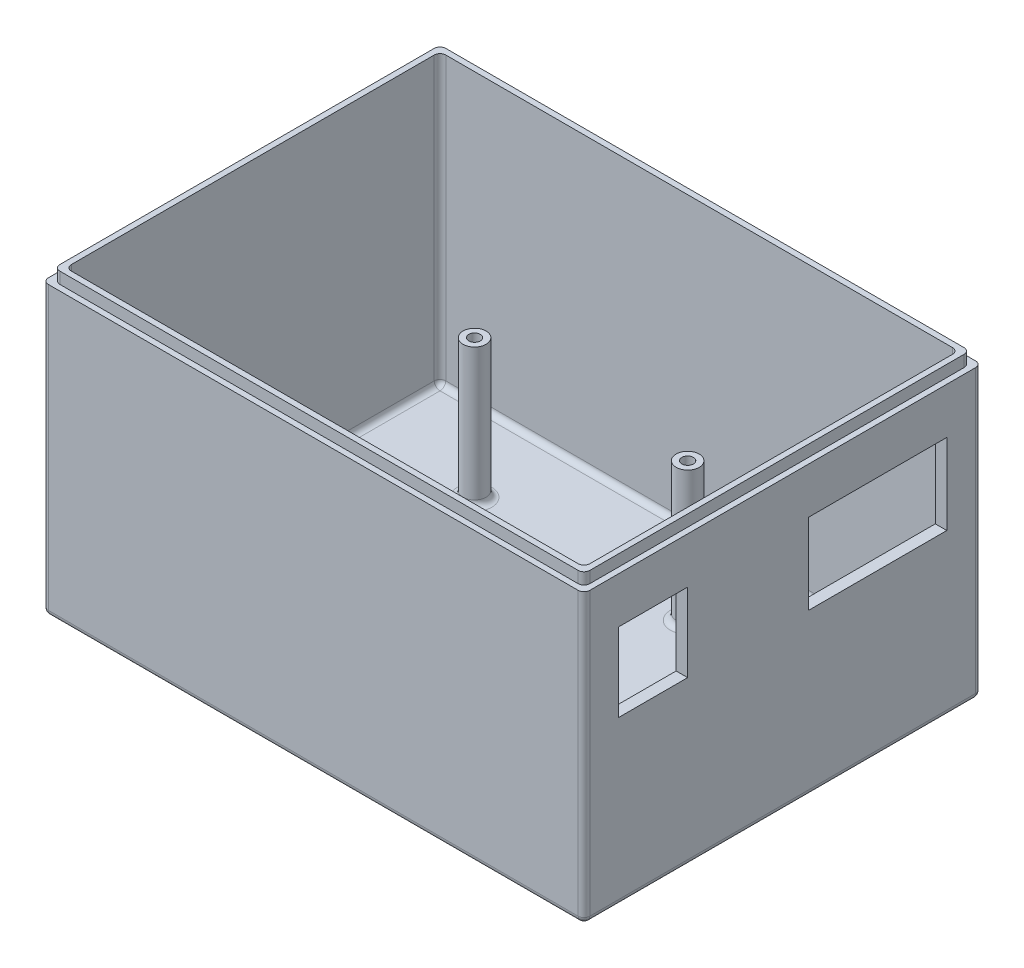
SolidWorks part; units mm, degrees
ref_plane "Front Plane" through (0, 0, 0) normal (0, 0, 1) x (1, 0, 0)
ref_plane "Top Plane" through (0, 0, 0) normal (0, 1, 0) x (1, 0, 0)
ref_plane "Right Plane" through (0, 0, 0) normal (1, 0, 0) x (0, 0, -1)
sketch "Sketch1" plane through (0, 0, 0) normal (0, 1, 0) x (1, 0, 0)
  line L1 (45, -32.5) -> (-45, -32.5)
  line L2 (45, -32.5) -> (45, 32.5)
  line L3 (45, 32.5) -> (-45, 32.5)
  line L4 (-45, -32.5) -> (-45, 32.5)
  line L5 (45, -32.5) -> (-45, 32.5) construction
  line L6 (45, 32.5) -> (-45, -32.5) construction
  point P0 (0, 0)
  dimension "D1" = 90
  dimension "D2" = 65
extrude "Boss-Extrude1" add sketch "Sketch1" along normal blind 50
shell "Shell1" thickness 2 removed face at (0, 50, 0) outward yes
sketch "Sketch2" plane through (0, 0, 0) normal (0, 1, 0) x (1, 0, 0)
  line L0 (45, -32.5) -> (45, 32.5) construction
  circle A0 centre (40, 0) radius 2.5
  circle A1 centre (-40, 0) radius 2.5
  dimension "D2" = 5
  dimension "D1" = 5
extrude "Boss-Extrude2" add sketch "Sketch2" along normal blind 10
sketch "Sketch3" plane through (0, 0, 0) normal (0, 1, 0) x (1, 0, 0)
  line L0 (45, 32.5) -> (-45, 32.5) construction
  line L1 (45, -32.5) -> (45, 32.5) construction
  line L2 (-45, -32.5) -> (45, -32.5) construction
  line L3 (-45, 32.5) -> (-45, -32.5) construction
  circle A0 centre (40, 27.5) radius 2.5
  circle A1 centre (-40, -27.5) radius 2.6728
  dimension "D3" = 5
  dimension "D1" = 5
  dimension "D2" = 5
  dimension "D4" = 5
  dimension "D5" = 5
extrude "Boss-Extrude3" add sketch "Sketch3" along normal blind 4
sketch "Sketch5" plane through (0, 4, 0) normal (0, 1, 0) x (1, 0, 0)
  circle A0 centre (40, 27.5) radius 1
  circle A1 centre (-40, -27.5) radius 1
  dimension "D1" = 2
  dimension "D2" = 2
extrude "Cut-Extrude1" cut sketch "Sketch5" against normal blind 3
sketch "Sketch7" plane through (0, 0, 0) normal (0, 1, 0) x (1, 0, 0)
  line L0 (-45, -32.5) -> (45, -32.5) construction
  line L1 (45, 32.5) -> (-45, 32.5) construction
  line L2 (-45, 32.5) -> (-45, -32.5) construction
  circle A0 centre (-25, -18.5) radius 2
  circle A1 centre (-25, 18.5) radius 2
  circle A2 centre (12, 18.5) radius 2
  circle A3 centre (12, -18.5) radius 2
  dimension "D1" = 14
  dimension "D2" = 4
  dimension "D4" = 4
  dimension "D6" = 20
  dimension "D7" = 20
  dimension "D3" = 14
  dimension "D5" = 37
  dimension "D8" = 37
extrude "Boss-Extrude5" add sketch "Sketch7" along normal blind 24 contours A2 | A0 | A1 | A3
sketch "Sketch11" plane through (0, 24, 0) normal (0, 1, 0) x (1, 0, 0)
  circle A0 centre (12, 18.5) radius 1
  circle A1 centre (-25, 18.5) radius 1
  circle A2 centre (-25, -18.5) radius 1
  circle A3 centre (12, -18.5) radius 1
  dimension "D1" = 2
  dimension "D2" = 2
  dimension "D3" = 2
  dimension "D4" = 2
extrude "Cut-Extrude2" cut sketch "Sketch11" against normal blind 4
sketch "Sketch12" plane through (47, 0, 0) normal (1, 0, 0) x (0, 0, -1)
  line L1 (28.5, 40) -> (4.5, 40)
  line L2 (28.5, 40) -> (28.5, 26)
  line L3 (28.5, 26) -> (4.5, 26)
  line L4 (4.5, 40) -> (4.5, 26)
  line L7 (-34.5, 50) -> (34.5, 50) construction
  line L9 (-28.5, 40) -> (-16.5, 40)
  line L10 (-28.5, 40) -> (-28.5, 26.378)
  line L11 (-28.5, 26.378) -> (-16.5, 26.378)
  line L12 (-16.5, 40) -> (-16.5, 26.378)
  line L13 (32.5, 50) -> (32.5, 0) construction
  line L14 (-32.5, 50) -> (-32.5, 0) construction
  dimension "D1" = 4
  dimension "D2" = 14
  dimension "D3" = 10
  dimension "D4" = 24
  dimension "D5" = 4
  dimension "D6" = 12
extrude "Cut-Extrude3" cut sketch "Sketch12" against normal blind 4
sketch "Sketch13" plane through (0, 50, 0) normal (0, 1, 0) x (1, 0, 0)
  line L14 (46, -33.5) -> (46, 33.5)
  line L15 (-46, -33.5) -> (46, -33.5)
  line L16 (-46, 33.5) -> (-46, -33.5)
  line L17 (46, 33.5) -> (-46, 33.5)
  line L18 (46, -33.5) -> (46, 33.5)
  line L19 (-46, -33.5) -> (46, -33.5)
  line L20 (-46, 33.5) -> (-46, -33.5)
  line L21 (46, 33.5) -> (-46, 33.5)
  dimension "D1" = 1
extrude "Cut-Extrude4" cut sketch "Sketch13" against normal blind 2 flip side to cut
fillet "Fillet1" radius 1 4 edges at (0, 0, -32.5) (45, 0, 0) (0, 0, 32.5) (-45, 0, 0)
fillet "Fillet2" radius 1 8 edges at (44.7071, 0.2929, 32.2071) (44.7071, 0.2929, -32.2071) (-44.7071, 0.2929, 32.2071) (-44.7071, 0.2929, -32.2071) (45, 25.5, 32.5) (45, 25.5, -32.5) (-45, 25.5, 32.5) (-45, 25.5, -32.5)
fillet "Fillet3" radius 1 8 edges at (-40, 0, 30.1728) (40, 0, -25) (40, 0, 2.5) (12, 0, 20.5) (12, 0, -16.5) (-25, 0, 20.5) (-25, 0, -16.5) (-40, 0, -2.5)
fillet "Fillet4" radius 1 8 edges at (0, -2, 34.5) (-47, 23, 34.5) (-47, -2, 0) (-47, 23, -34.5) (0, -2, -34.5) (47, 23, -34.5) (47, -2, 0) (47, 23, 34.5)
fillet "Fillet5" radius 1 4 edges at (-46, 49, 33.5) (-46, 49, -33.5) (46, 49, -33.5) (46, 49, 33.5)
fillet "Fillet6" radius 1 4 edges at (-25, 20, 19.5) (-25, 20, -17.5) (12, 20, -17.5) (12, 20, 19.5)
fillet "Fillet7" radius 1 2 edges at (-40, 1, 28.5) (40, 1, -26.5)
sketch "Sketch15" plane through (0, 10, 0) normal (0, 1, 0) x (1, 0, 0)
  circle A0 centre (-40, 0) radius 1.25
  circle A1 centre (40, 0) radius 1.25
  dimension "D1" = 2.5
  dimension "D2" = 2.5
extrude "Cut-Extrude5" cut sketch "Sketch15" against normal through all
